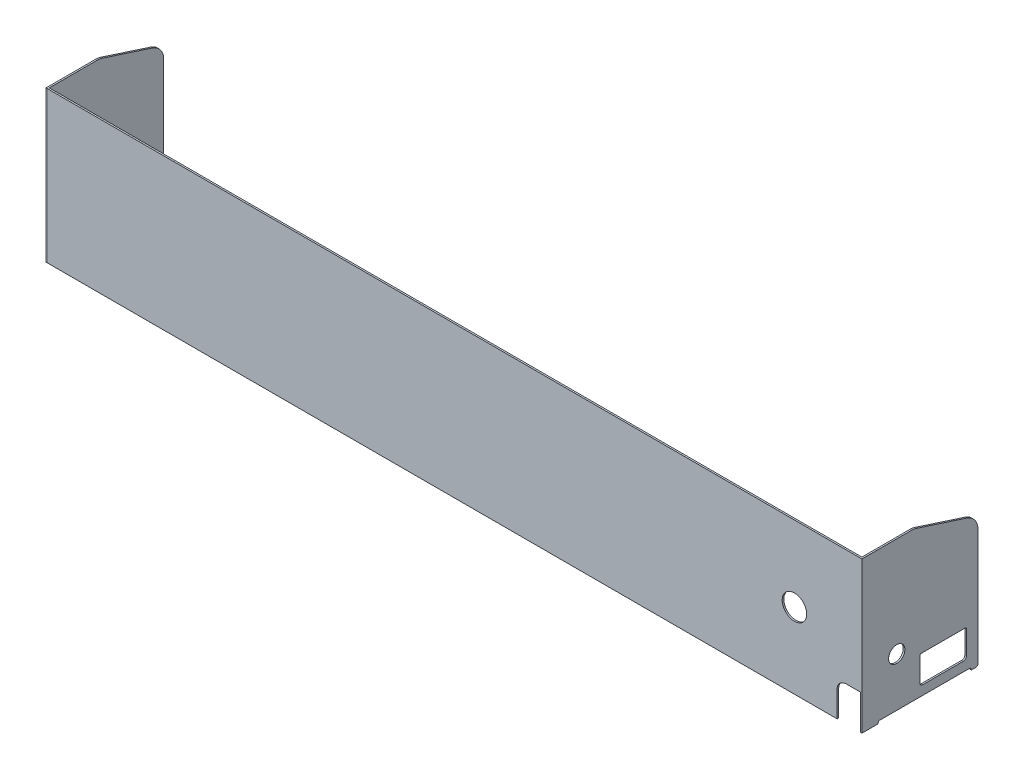
SolidWorks part; units mm, degrees
ref_plane "Front Plane" through (0, 0, 0) normal (0, 0, 1) x (1, 0, 0)
ref_plane "Top Plane" through (0, 0, 0) normal (0, 1, 0) x (1, 0, 0)
ref_plane "Right Plane" through (0, 0, 0) normal (1, 0, 0) x (0, 0, -1)
sketch "Sketch1" plane through (0, 0, 0) normal (0, 0, 1) x (1, 0, 0)
  line L0 (0, 283.3898) -> (0, -294.2373) construction
  line L1 (-518.8701, 0) -> (517.0621, 0) construction
  line L2 (175, -17.5) -> (169, -17.5)
  line L3 (-175, 32.5) -> (175, 32.5)
  line L4 (-175, 32.5) -> (-175, -32.5)
  line L5 (-175, -32.5) -> (165, -32.5)
  line L6 (175, 32.5) -> (175, -17.5)
  line L7 (165, -21.5) -> (165, -32.5)
  arc A0 (169, -17.5) -> (165, -21.5) centre (169, -21.5) ccw
  point P13 (165, -17.5)
  dimension "D5" = 4
  dimension "D1" = 350
  dimension "D2" = 65
  dimension "D3" = 10
  dimension "D4" = 15
extrude "Back Wall" add sketch "Sketch1" along normal blind 0.7
ref_plane "Right_wall Plane" through (-175, 0, 0) normal (-1, 0, 0) x (0, 0, 1)
sketch "Sketch2" plane through (-175, 0, 0) normal (-1, 0, 0) x (0, 0, 1)
  line L0 (-62.6179, 0) -> (70.933, 0) construction
  line L1 (0, 60.0387) -> (0, -42.0887) construction
  line L2 (-48.3, -32.5) -> (-46.5, -32.5)
  line L3 (-49.3, -31.5) -> (-49.3, 18.5)
  line L4 (0.7, 32.5) -> (0.7, -32.5) construction
  line L5 (0.7, 32.5) -> (-20.6433, 32.5)
  line L6 (0.7, 32.5) -> (0.7, -32.5)
  line L7 (-44.4529, 25.1607) -> (-22.7963, 32.1607)
  line L8 (-46.3, -32.3) -> (-46.3, -32.2)
  line L9 (-45.6, -31.5) -> (-7, -31.5)
  line L10 (-6.3, -32.2) -> (-6.3, -32.3)
  line L11 (-6.1, -32.5) -> (0.7, -32.5)
  line L13 (-43.8, -15.5) -> (-24.8, -15.5)
  line L14 (-44.3, -16) -> (-44.3, -26.3)
  line L15 (-43.1, -27.5) -> (-25.5, -27.5)
  line L16 (-24.3, -16) -> (-24.3, -26.3)
  arc A0 (-44.4529, 25.1607) -> (-49.3, 18.5) centre (-42.3, 18.5) ccw
  arc A1 (-20.6433, 32.5) -> (-22.7963, 32.1607) centre (-20.6433, 25.5) ccw
  arc A2 (-48.3, -32.5) -> (-49.3, -31.5) centre (-48.3, -31.5) cw
  arc A3 (-24.8, -15.5) -> (-24.3, -16) centre (-24.8, -16) cw
  arc A4 (-43.8, -15.5) -> (-44.3, -16) centre (-43.8, -16) ccw
  arc A5 (-24.3, -26.3) -> (-25.5, -27.5) centre (-25.5, -26.3) cw
  arc A6 (-43.1, -27.5) -> (-44.3, -26.3) centre (-43.1, -26.3) cw
  arc A7 (-45.6, -31.5) -> (-46.3, -32.2) centre (-45.6, -32.2) ccw
  arc A8 (-46.3, -32.3) -> (-46.5, -32.5) centre (-46.5, -32.3) cw
  arc A9 (-6.1, -32.5) -> (-6.3, -32.3) centre (-6.1, -32.3) cw
  arc A10 (-7, -31.5) -> (-6.3, -32.2) centre (-7, -32.2) cw
  circle A11 centre (-14.3, -10.5) radius 3.5
  point P16 (-49.3, 23.594)
  point P19 (-21.7465, 32.5)
  point P22 (-39.5789, -38.1792)
  point P43 (-46.3, -32.5)
  dimension "D4" = 7
  dimension "D5" = 7
  dimension "D6" = 1
  dimension "D16" = 0.5
  dimension "D17" = 1.2
  dimension "D18" = 0.7
  dimension "D19" = 0.2
  dimension "D20" = 0.2
  dimension "D21" = 0.7
  dimension "D22" = 7
  dimension "D1" = 50
  dimension "D3" = 50
  dimension "D7" = 3
  dimension "D8" = 1
  dimension "D9" = 7
  dimension "D10" = 2
  dimension "D11" = 22.7599
  dimension "D12" = 2
  dimension "D13" = 4
  dimension "D14" = 20
  dimension "D15" = 12
  dimension "D23" = 10
  dimension "0.5cm" = 5
extrude "Right Wall" add sketch "Sketch2" along normal blind 0.7 separate body
ref_plane "Left_wall Plane" through (175, 0, 0) normal (1, 0, 0) x (0, 0, -1)
ref_plane "Mid Plane" through (0, 0, 0) normal (1, 0, 0) x (0, 0, -1)
mirror "Mirror8" about plane through (0, 0, 0) normal (1, 0, 0) of "Right Wall"
sketch "Sketch3" plane through (0, 0, 0) normal (1, 0, 0) x (0, 0, -1)
sketch "Sketch4" plane through (0, 0, 0.7) normal (0, 0, 1) x (1, 0, 0)
  circle A0 centre (146.6398, 0) radius 5.2775
extrude "Cut-Extrude2" cut sketch "Sketch4" against normal blind 10
